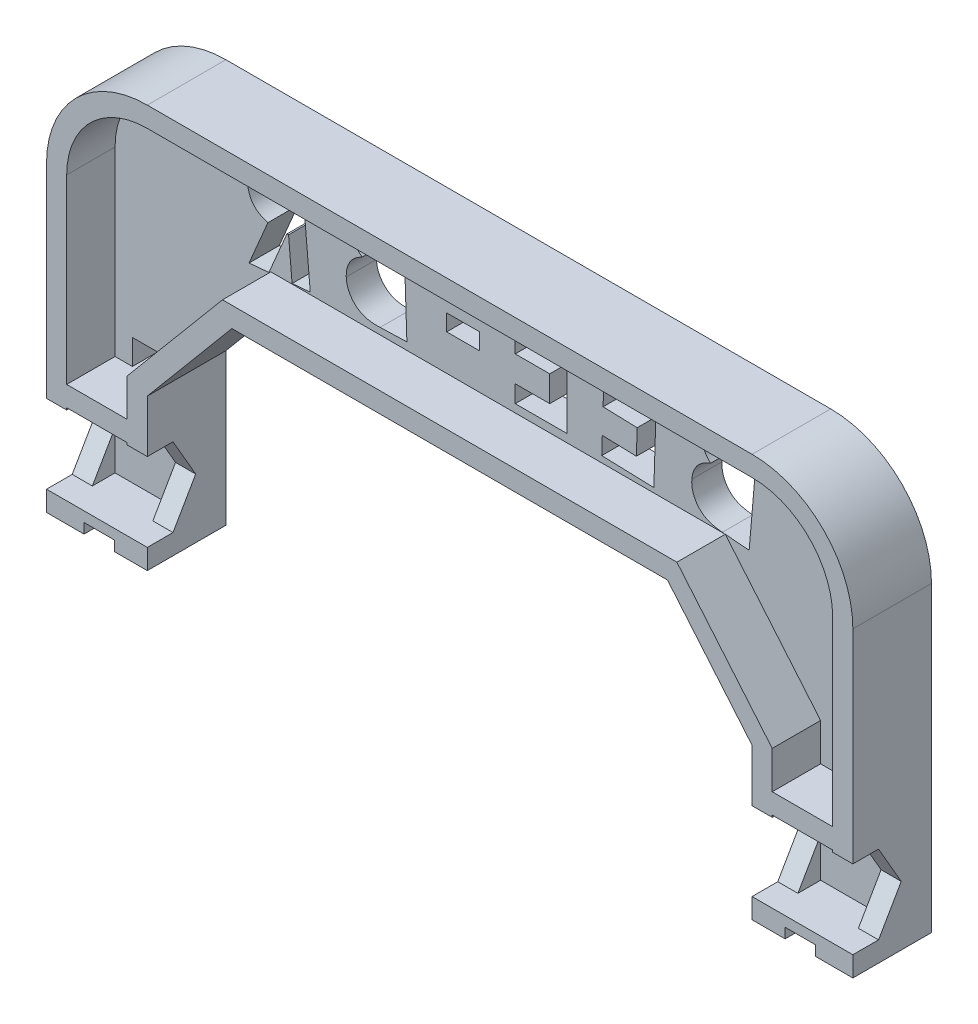
SolidWorks part; units mm, degrees
ref_plane "Plano frontal" through (0, 0, 0) normal (0, 0, 1) x (1, 0, 0)
ref_plane "Plano superior" through (0, 0, 0) normal (0, 1, 0) x (1, 0, 0)
ref_plane "Plano direito" through (0, 0, 0) normal (1, 0, 0) x (0, 0, -1)
sketch "Esboço1" plane through (0, 0, 0) normal (0, 0, 1) x (1, 0, 0)
  line L0 (-30, -25) -> (-30, -10)
  line L1 (-30, 15) -> (30, 15)
  line L2 (-40, 5) -> (-40, -25)
  line L3 (-40, -25) -> (40, -25)
  line L4 (40, 5) -> (40, -25)
  line L5 (-30, -10) -> (-21.609, 0)
  line L6 (21.609, 0) -> (30, -10)
  line L7 (-21.609, 0) -> (21.609, 0)
  line L8 (30, -10) -> (30, -25)
  line L9 (-38, 5) -> (-38, -23)
  line L10 (-38, -23) -> (38, -23)
  line L11 (38, 5) -> (38, -23)
  line L12 (-30, 13) -> (30, 13)
  line L13 (-32, -25) -> (-32, -9.2721)
  line L14 (-32, -9.2721) -> (-22.5416, 2)
  line L15 (-22.5416, 2) -> (22.5416, 2)
  line L16 (22.5416, 2) -> (32, -9.2721)
  line L17 (32, -9.2721) -> (32, -25)
  line L18 (-32, -13) -> (-38, -13)
  line L19 (30, -13) -> (40, -13)
  line L20 (-38, -15) -> (-32, -15)
  line L21 (30, -15) -> (40, -15)
  line L22 (-38, -15) -> (-40, -15)
  line L23 (-38, -13) -> (-40, -13)
  line L24 (-38, -23) -> (-40, -23)
  line L25 (-32, -13) -> (-30, -13)
  line L26 (-32, -15) -> (-30, -15)
  line L27 (38, -23) -> (40, -23)
  arc A0 (40, 5) -> (30, 15) centre (30, 5) ccw
  arc A1 (-40, 5) -> (-30, 15) centre (-30, 5) cw
  arc A2 (38, 5) -> (30, 13) centre (30, 5) ccw
  arc A3 (-38, 5) -> (-30, 13) centre (-30, 5) cw
  point P0 (0, 0)
  dimension "D10" = 10
  dimension "D1" = 80
  dimension "D2" = 10
  dimension "D3" = 10
  dimension "D4" = 25
  dimension "D5" = 130
  dimension "D6" = 15
  dimension "D7" = 15
  dimension "D8" = 15
  dimension "D9" = 130
  dimension "D12" = 2
  dimension "D13" = 8
  dimension "D11" = 2
extrude "Ressalto-extrusão1" add sketch "Esboço1" along normal blind 3 contours L9 A3 L12 A2 L11 L10 L17 L3 L4 A0 L1 A1 L2 L13 | L17 L10 L8 L3 | L21 L17 L10 L11 | L17 L16 L15 L14 L13 L10 L0 L5 L7 L6 L8 | A3 L9 L18 L13 L14 L15 L16 L17 L19 L11 A2 L12 | L17 L21 L11 L19 | L20 L9 L10 L13 | L13 L3 L0 L10 | L9 L20 L13 L18 | L27 L10 L17 L3 L4 | L11 L27 L4 L21 | L11 L21 L4 L19 | L8 L21 L17 L19 | L21 L8 L10 L17 | L24 L9 L22 L2 | L9 L23 L2 L22 | L13 L26 L0 L25 | L26 L13 L10 L0 | L10 L24 L2 L3 L13 region at (-31, -14, 0) region at (-31, -19, 0) region at (-31, -12.3427, 0) region at (-31, -24, 0) region at (-35, -14, 0) region at (-35, -19, 0) region at (0, 4.3689, 0) region at (-36, -24, 0) region at (31, -24, 0) region at (31, -19, 0) region at (-39, -14, 0) region at (-39, -19, 0) region at (-39, -12.1524, 0) region at (31, -14, 0) region at (35, -19, 0) region at (36, -24, 0) region at (35, -14, 0) region at (39, -19, 0) region at (39, -14, 0)
extrude "Ressalto-extrusão2" add sketch "Esboço1<4>" along normal blind 7.8 contours L10 L24 L2 L3 L13 | L13 L3 L0 L10 | L9 L20 L13 L18 | L13 L26 L0 L25 | L9 L23 L2 L22 | L13 L25 L0 L5 L7 L6 L8 L19 L17 L16 L15 L14 | L9 A3 L12 A2 L11 L19 L4 A0 L1 A1 L2 L23 | L11 L21 L4 L19 | L8 L21 L17 L19 | L17 L10 L8 L3 | L27 L10 L17 L3 L4 | L17 L21 L11 L19 | L26 L13 L10 L0 | L24 L9 L22 L2 | L11 L27 L4 L21 | L21 L8 L10 L17 region at (-31, -14, 0) region at (-31, -19, 0) region at (-31, -12.3427, 0) region at (-31, -24, 0) region at (-35, -14, 0) region at (-36, -24, 0) region at (31, -24, 0) region at (31, -19, 0) region at (-39, -14, 0) region at (-39, -19, 0) region at (-39, -12.1524, 0) region at (31, -14, 0) region at (36, -24, 0) region at (35, -14, 0) region at (39, -19, 0) region at (39, -14, 0)
sketch "Esboço1<4>" plane through (0, 0, 0) normal (0, 0, 1) x (1, 0, 0) same geometry as "Esboço1"
extrude "Ressalto-extrusão3" add sketch "Esboço1<5>" along normal blind 6.5 and the other way blind 1 from vertex contours L24 L9 L22 L2 | L10 L24 L2 L3 L13 | L13 L3 L0 L10 | L13 L26 L0 L25 | L9 L20 L13 L18 | L9 L23 L2 L22 | L26 L13 L10 L0 | L27 L10 L17 L3 L4 | L17 L10 L8 L3 | L21 L8 L10 L17 | L8 L21 L17 L19 | L11 L27 L4 L21 | L11 L21 L4 L19 | L17 L21 L11 L19 region at (-31, -14, 0) region at (-31, -19, 0) region at (-31, -24, 0) region at (-35, -14, 0) region at (-36, -24, 0) region at (31, -24, 0) region at (31, -19, 0) region at (-39, -14, 0) region at (-39, -19, 0) region at (31, -14, 0) region at (36, -24, 0) region at (35, -14, 0) region at (39, -19, 0) region at (39, -14, 0) starting at point (-40, -25, 7.8)
sketch "Esboço1<5>" plane through (0, 0, 0) normal (0, 0, 1) x (1, 0, 0) same geometry as "Esboço1"
sketch "Esboço2" plane through (-40, 0, 0) normal (-1, 0, 0) x (0, 0, 1)
  line L0 (14.3, -25) -> (0, -25) construction
  line L1 (5.2517, -23) -> (9.755, -23)
  line L2 (9.755, -23) -> (12.0067, -19.1)
  line L3 (12.0067, -19.1) -> (9.755, -15.2)
  line L4 (9.755, -15.2) -> (5.2517, -15.2)
  line L5 (5.2517, -15.2) -> (3, -19.1)
  line L6 (3, -19.1) -> (5.2517, -23)
  line L7 (14.3, -23) -> (3, -23) construction
  line L8 (0, 5) -> (0, -25) construction
  circle A0 centre (7.5033, -19.1) radius 3.9 construction
  dimension "D1" = 7.8
  dimension "D2" = 3
extrude "Corte-extrusão1" cut sketch "Esboço2" against normal through all
sketch "Esboço3" plane through (0, 0, 0) normal (0, 0, -1) x (-1, 0, 0)
  arc A0 (-27.5068, 1.5596) -> (26.6133, 1.5596) centre (-0.4467, -270.4387) cw construction
  text T0 "BEE-BR" font "Century Gothic" height in points 36
extrude "Corte-extrusão2" cut sketch "Esboço3" against normal blind 90.8
delete or keep bodies "Corpo-Excluir1" type delete bodies bodies 109
delete or keep bodies "Corpo-Excluir2" type delete bodies bodies 108
sketch "Esboço4" plane through (-40, 0, 0) normal (-1, 0, 0) x (0, 0, 1)
  circle A0 centre (7.5033, -19.1) radius 3.9
sketch "Esboço5" plane through (40, 0, 0) normal (1, 0, 0) x (0, 0, -1)
  circle A0 centre (-7.5033, -19.1) radius 3.9
delete or keep bodies "Corpo-Excluir3" type delete bodies bodies 111 112 110
sketch "Esboço6" plane through (0, -25, 0) normal (0, -1, 0) x (1, 0, 0)
  line L1 (-40, 14.3) -> (40, 14.3)
  line L2 (-40, 14.3) -> (-40, 7.8)
  line L3 (-40, 7.8) -> (40, 7.8)
  line L4 (40, 14.3) -> (40, 7.8)
extrude "Corte-extrusão3" cut sketch "Esboço6" against normal up to vertex (12 mm away) up to point (40, -13, 7.8)
sketch "Esboço8" plane through (0, 0, 7.8) normal (0, 0, 1) x (1, 0, 0)
  line L0 (-38, -13) -> (-32, -13) construction
  line L1 (-36.2789, -13) -> (-33.2789, -13)
  line L2 (-36.2789, -13) -> (-36.2789, -10.5)
  line L3 (-36.2789, -10.5) -> (-33.2789, -10.5)
  line L4 (-33.2789, -13) -> (-33.2789, -10.5)
  line L6 (-36.2789, -24) -> (-33.2789, -24)
  line L7 (-36.2789, -24) -> (-36.2789, -25)
  line L8 (-36.2789, -25) -> (-33.2789, -25)
  line L9 (-33.2789, -24) -> (-33.2789, -25)
  line L10 (-40, -25) -> (-30, -25) construction
  line L11 (-34.7789, -25) -> (-34.7789, -13) construction
  dimension "D1" = 3
  dimension "D2" = 3
  dimension "D3" = 1
  dimension "D4" = 2.5
extrude "Corte-extrusão4" cut sketch "Esboço8" against normal blind 19
mirror "Espelhar1" about plane through (0, 0, 0) normal (1, 0, 0) of "Corte-extrusão4"
